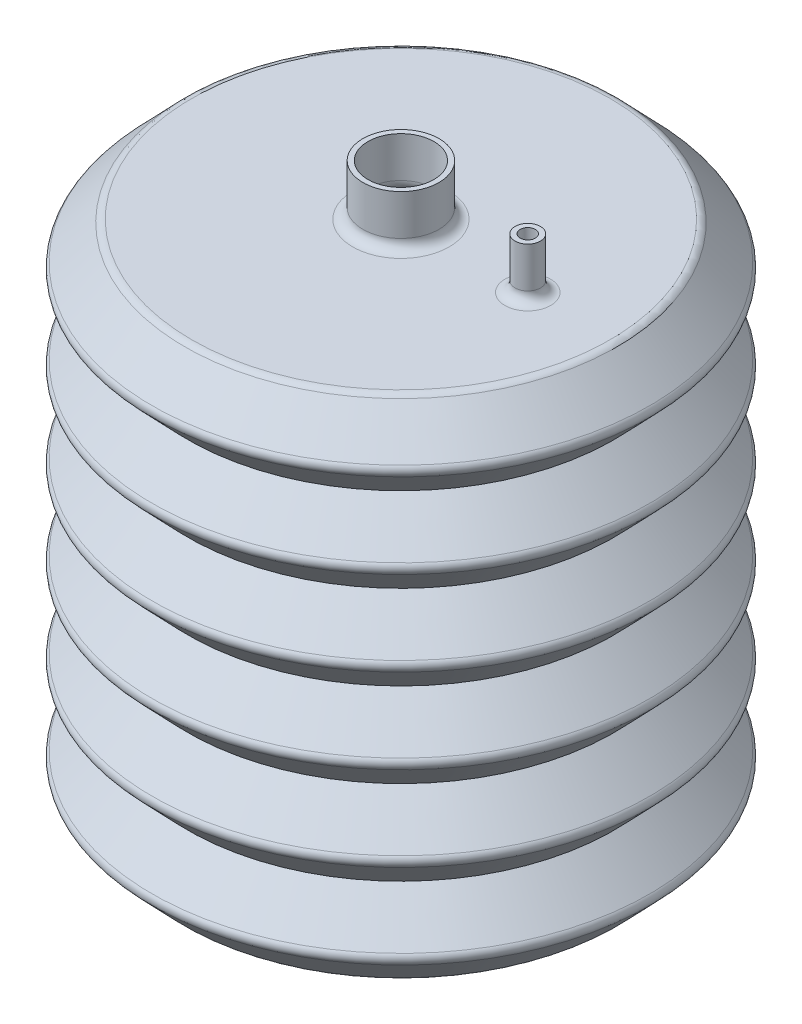
SolidWorks part; units mm, degrees
material "Perspex (TM) Folha de Acrílico GS Fundido"
ref_plane "Plano frontal" through (0, 0, 0) normal (0, 0, 1) x (1, 0, 0)
ref_plane "Plano superior" through (0, 0, 0) normal (0, 1, 0) x (1, 0, 0)
ref_plane "Plano direito" through (0, 0, 0) normal (1, 0, 0) x (0, 0, -1)
sketch "Esboço1" plane through (0, 0, 0) normal (1, 0, 0) x (0, 0, -1)
  line L0 (0, 0) -> (0, 121.08) construction
  line L1 (0, 0) -> (41.1476, 0)
  line L2 (42.5903, 0.6149) -> (49.0408, 7.3342)
  line L3 (49.0408, 9.3325) -> (42, 16.6667)
  line L4 (50, 8.3333) -> (42, 8.3333) construction
  line L5 (42, 16.6667) -> (49.0408, 24.0008)
  line L6 (49.0408, 25.9992) -> (42, 33.3333)
  line L7 (50, 25) -> (42, 25) construction
  line L8 (42, 33.3333) -> (49.0408, 40.6675)
  line L9 (49.0408, 42.6658) -> (42, 50)
  line L10 (50, 41.6667) -> (42, 41.6667) construction
  line L11 (42, 50) -> (49.0408, 57.3342)
  line L12 (49.0408, 59.3325) -> (42, 66.6667)
  line L13 (50, 58.3333) -> (42, 58.3333) construction
  line L14 (41.2158, 100) -> (9.5, 100)
  line L15 (42, 66.6667) -> (49.0408, 74.0008)
  line L16 (49.0408, 75.9992) -> (42, 83.3333)
  line L17 (50, 75) -> (42, 75) construction
  line L18 (42, 83.3333) -> (49.0408, 90.6675)
  line L19 (49.0408, 92.6658) -> (42.5431, 99.4343)
  line L20 (50, 91.6667) -> (42, 91.6667) construction
  line L21 (0, 100) -> (0, 0)
  line L22 (7.5, 102) -> (7.5, 110)
  line L23 (7.5, 110) -> (0, 110)
  line L24 (0, 110) -> (0, 100)
  arc A0 (49.0408, 90.6675) -> (49.0408, 92.6658) centre (48, 91.6667) ccw
  arc A1 (49.0408, 74.0008) -> (49.0408, 75.9992) centre (48, 75) ccw
  arc A2 (49.0408, 57.3342) -> (49.0408, 59.3325) centre (48, 58.3333) ccw
  arc A3 (49.0408, 40.6675) -> (49.0408, 42.6658) centre (48, 41.6667) ccw
  arc A4 (49.0408, 25.9992) -> (49.0408, 24.0008) centre (48, 25) cw
  arc A5 (49.0408, 7.3342) -> (49.0408, 9.3325) centre (48, 8.3333) ccw
  arc A6 (41.2158, 100) -> (42.5431, 99.4343) centre (41.2158, 98.1601) cw
  arc A7 (9.5, 100) -> (7.5, 102) centre (9.5, 102) cw
  arc A8 (41.1476, 0) -> (42.5903, 0.6149) centre (41.1476, 2) ccw
  point P18 (42, 100)
  point P51 (42, 0)
  dimension "D3" = 2
  dimension "D6" = 2
  dimension "D7" = 2
  dimension "D10" = 2
  dimension "D1" = 6
  dimension "D2" = 100
  dimension "D4" = 8
  dimension "D5" = 100
  dimension "D8" = 10
  dimension "D9" = 15
revolve "Revolução1" add sketch "Esboço1" angle 360 about L0
sketch "Esboço2" plane through (0, 100, 0) normal (0, 1, 0) x (1, 0, 0)
  circle A0 centre (25, 0) radius 2.5
  point P2 (0, 0)
  point P4 (0, 0)
  dimension "D1" = 5
  dimension "D2" = 25
extrude "Ressalto-extrusão1" add sketch "Esboço2" along normal blind 10
fillet "Filete1" radius 2 1 edges at (25, 100, 2.5)
shell "Casca2" thickness 1 removed face at (25, 110, 2.5) removed face at (0, 110, -7.5)
sketch "Esboço5" plane through (0, 0, 0) normal (1, 0, 0) x (0, 0, -1)
  line L0 (225.9034, 217.7073) -> (841.9034, 217.7073) construction
